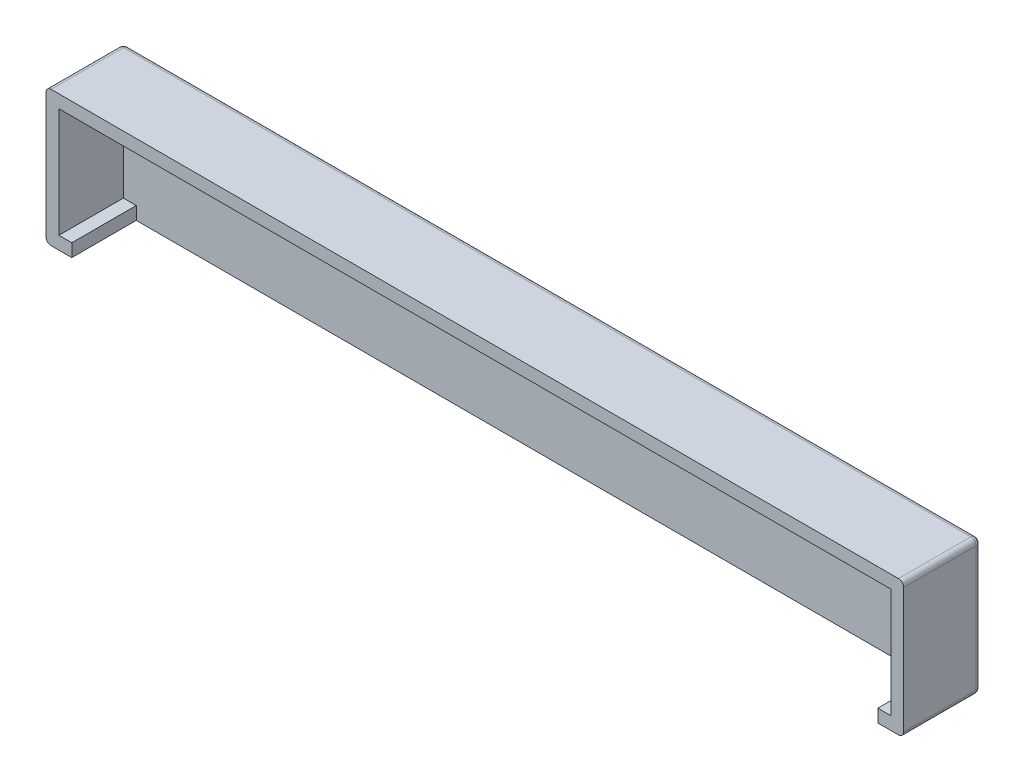
SolidWorks part; units mm, degrees
ref_plane "Front Plane" through (0, 0, 0) normal (0, 0, 1) x (1, 0, 0)
ref_plane "Top Plane" through (0, 0, 0) normal (0, 1, 0) x (1, 0, 0)
ref_plane "Right Plane" through (0, 0, 0) normal (1, 0, 0) x (0, 0, -1)
sketch "Sketch1" plane through (0, 0, 0) normal (0, 0, 1) x (1, 0, 0)
  line L1 (0, 0) -> (211.1375, 0)
  line L2 (0, 0) -> (0, 33.3375)
  line L3 (0, 33.3375) -> (211.1375, 33.3375)
  line L4 (211.1375, 0) -> (211.1375, 33.3375)
  dimension "D1" = 211.1375
  dimension "D2" = 33.3375
extrude "Boss-Extrude1" add sketch "Sketch1" along normal blind 3.175 contours L3 L4 L1 L2
sketch "Sketch2" plane through (0, 0, 3.175) normal (0, 0, 1) x (1, 0, 0)
  line L11 (6.35, 0) -> (6.35, 3.175)
  line L12 (204.7875, 0) -> (204.7875, 3.175)
  line L13 (0, 0) -> (6.35, 0)
  line L14 (204.7875, 3.175) -> (207.9625, 3.175)
  line L15 (207.9625, 3.175) -> (207.9625, 30.1625)
  line L16 (3.175, 3.175) -> (207.9625, 3.175)
  line L17 (3.175, 30.1625) -> (3.175, 3.175)
  line L18 (207.9625, 30.1625) -> (3.175, 30.1625)
  line L19 (207.9625, 3.175) -> (207.9625, 30.1625)
  line L20 (3.175, 3.175) -> (6.35, 3.175)
  line L21 (3.175, 30.1625) -> (3.175, 3.175)
  line L22 (207.9625, 30.1625) -> (3.175, 30.1625)
  line L23 (0, 33.3375) -> (0, 0)
  line L24 (0, 0) -> (211.1375, 0)
  line L25 (211.1375, 0) -> (211.1375, 33.3375)
  line L26 (211.1375, 33.3375) -> (0, 33.3375)
  line L27 (0, 33.3375) -> (0, 0)
  line L28 (204.7875, 0) -> (211.1375, 0)
  line L29 (211.1375, 0) -> (211.1375, 33.3375)
  line L30 (211.1375, 33.3375) -> (0, 33.3375)
  point P8 (18.292, 0)
  point P9 (6.35, 1.5875)
  dimension "D3" = 6.35
  dimension "D4" = 6.35
  dimension "D1" = 3.175
  dimension "D2" = 0
extrude "Boss-Extrude2" add sketch "Sketch2" along direction (0, 0, -1) on the side of the normal offset from surface (15.875 mm away) 19.05 up to face at (105.5688, 16.6687, 0)
fillet "Fillet1" radius 1.27 8 edges at (105.5688, 0, 0) (0, 0, 9.525) (0, 16.6687, 0) (0, 33.3375, 9.525) (105.5688, 33.3375, 0) (211.1375, 16.6687, 0) (211.1375, 0, 9.525) (211.1375, 33.3375, 9.525)
